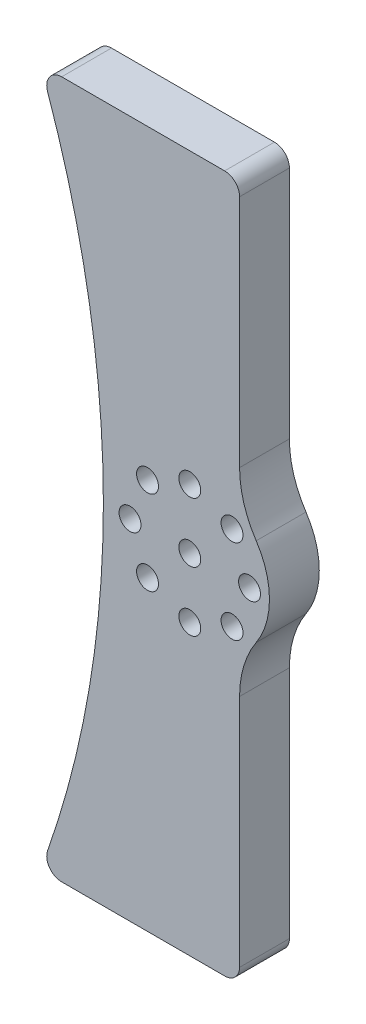
SolidWorks part; units mm, degrees
material "ABS"
ref_plane "正面" through (0, 0, 0) normal (0, 0, 1) x (1, 0, 0)
ref_plane "平面" through (0, 0, 0) normal (0, 1, 0) x (1, 0, 0)
ref_plane "右側面" through (0, 0, 0) normal (1, 0, 0) x (0, 0, -1)
sketch "ｽｹｯﾁ1" plane through (0, 0, 0) normal (0, 0, 1) x (1, 0, 0)
  line L0 (0, 0) -> (0, 70) construction
  line L1 (-5, 70) -> (5, 70)
  line L2 (-5, 70) -> (-5, 44.9499)
  line L3 (-5, 0) -> (5, 0)
  line L4 (5, 70) -> (5, 44.9499)
  line L5 (-5, 25.0501) -> (-5, 0)
  line L6 (5, 25.0501) -> (5, 0)
  circle A0 centre (0, 35) radius 1.1
  circle A1 centre (0, 35) radius 6 construction
  circle A2 centre (0, 29) radius 1.1
  circle A3 centre (-4.2426, 30.7574) radius 1.1
  circle A4 centre (-6, 35) radius 1.1
  circle A5 centre (-4.2426, 39.2426) radius 1.1
  circle A6 centre (0, 41) radius 1.1
  circle A7 centre (4.2426, 39.2426) radius 1.1
  circle A8 centre (6, 35) radius 1.1
  circle A9 centre (4.2426, 30.7574) radius 1.1
  arc A10 (-6.6667, 39.4222) -> (-6.6667, 30.5778) centre (0, 35) ccw
  arc A11 (6.6667, 30.5778) -> (6.6667, 39.4222) centre (0, 35) ccw
  arc A12 (-6.6667, 39.4222) -> (-5, 44.9499) centre (-15, 44.9499) ccw
  arc A13 (-6.6667, 30.5778) -> (-5, 25.0501) centre (-15, 25.0501) cw
  arc A14 (5, 25.0501) -> (6.6667, 30.5778) centre (15, 25.0501) cw
  arc A15 (5, 44.9499) -> (6.6667, 39.4222) centre (15, 44.9499) ccw
  point P29 (0, 35)
  point P35 (-5, 28.755)
  point P38 (5, 28.755)
  dimension "D3" = 2.2
  dimension "D5" = 12
  dimension "D6" = 2.2
  dimension "D8" = 16
  dimension "D9" = 10
  dimension "D1" = 10
  dimension "D2" = 70
  dimension "D4" = 35
  dimension "D7" = 8
extrude "ﾎﾞｽ - 押し出し1" add sketch "ｽｹｯﾁ1" along normal blind 5
sketch "ｽｹｯﾁ2" plane through (0, 0, 0) normal (0, 0, -1) x (-1, 0, 0)
  line L0 (5, 25.0501) -> (5, 0) construction
  line L1 (5, 70) -> (5, 44.9499) construction
  line L2 (5, 25.0501) -> (5, 0)
  line L3 (5, 70) -> (5, 44.9499)
  line L4 (5, 70) -> (15, 70)
  line L5 (5, 0) -> (15, 0)
  arc A0 (6.6667, 30.5778) -> (5, 25.0501) centre (15, 25.0501) ccw construction
  arc A1 (6.6667, 30.5778) -> (6.6667, 39.4222) centre (0, 35) ccw construction
  arc A2 (5, 44.9499) -> (6.6667, 39.4222) centre (15, 44.9499) ccw construction
  arc A3 (6.6667, 30.5778) -> (5, 25.0501) centre (15, 25.0501) ccw
  arc A4 (6.6667, 30.5778) -> (6.6667, 39.4222) centre (0, 35) ccw
  arc A5 (5, 44.9499) -> (6.6667, 39.4222) centre (15, 44.9499) ccw
  arc A6 (15, 70) -> (15, 0) centre (108.675, 35) ccw
  dimension "D1" = 200
  dimension "D2" = 10
extrude "ﾎﾞｽ - 押し出し2" add sketch "ｽｹｯﾁ2" against normal blind 5
fillet "ﾌｨﾚｯﾄ1" radius 1.5 4 edges at (5, 0, 2.5) (-15, 0, 2.5) (-15, 70, 2.5) (5, 70, 2.5)
